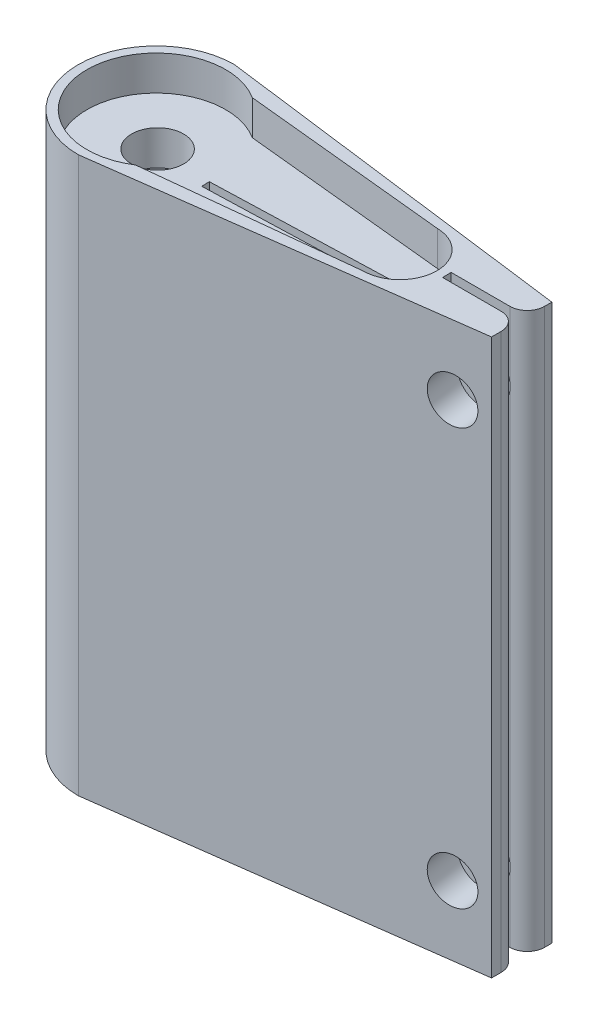
SolidWorks part; units mm, degrees
ref_plane "Front Plane" through (0, 0, 0) normal (0, 0, 1) x (1, 0, 0)
ref_plane "Top Plane" through (0, 0, 0) normal (0, 1, 0) x (1, 0, 0)
ref_plane "Right Plane" through (0, 0, 0) normal (1, 0, 0) x (0, 0, -1)
sketch "Sketch2" plane through (0, 0, 0) normal (0, 1, 0) x (1, 0, 0)
  line L0 (-24.822, 2.75) -> (-24.822, -2.75) construction
  line L1 (-26.9871, 0) -> (-9.8477, 0) construction
  line L2 (-5.9803, -0.2) -> (-5.98, -1.7573)
  line L3 (-5.9802, 0.3) -> (-10.372, 0.3)
  line L4 (-26.9871, 4.4282) -> (-5.9802, 1.719)
  line L5 (-26.9871, -4.5715) -> (-5.98, -1.7573)
  line L6 (-26.9871, 0) -> (-1.9871, 0) construction
  line L7 (-26.9871, -4.5715) -> (-2.3632, -1.0673) construction
  line L8 (-26.9871, 4.4282) -> (-5.9802, 2.3) construction
  line L9 (-10.372, 0.3) -> (-10.3556, -0.2)
  line L10 (-5.98, -1.7573) -> (-5.98, 5.1188) construction
  line L11 (-24.8218, 3.2918) -> (-12.9398, 2.0943)
  line L12 (-12.9872, -2.1664) -> (-24.8217, -3.4351)
  line L13 (-10.3556, -0.2) -> (-5.9803, -0.2)
  line L14 (-5.9802, 0.3) -> (-5.9802, 2.3)
  line L15 (-5.9802, 0.3) -> (-5.9802, -0.3836) construction
  circle A1 centre (-26.9871, 0) radius 1.5
  circle A3 centre (-26.9871, -0.0716) radius 4.4998
  circle A4 centre (-12.9872, -0.0358) radius 2.6366
  circle A6 centre (-12.9872, -0.0358) radius 2.1306
  circle A7 centre (-26.9871, -0.0716) radius 4.0002
  point P5 (-5.9802, -0.9787)
  dimension "D1" = 5.5
  dimension "D3" = 14
  dimension "D4" = 14
  dimension "D5" = 2
  dimension "D9" = 0
  dimension "D10" = 0
  dimension "D6" = 0
extrude "Boss-Extrude1" add sketch "Sketch2" along normal blind 30 contours A7 A1 | A7 L12 A3 L11 | A4 L11 A3 L12 | A6 L11 A4 L12 | A6 region at (-15.571, 0, 0.0394) region at (-19.2555, 0, 0.0535) region at (-24.3629, 0, 3.3143) region at (-12.9872, 0, 0.0358) region at (-30.8741, 0, 0.0717)
extrude "Boss-Extrude2" add sketch "Sketch2<3>" along normal blind 32 contours A7 L11 A3 L4 L5 L12 | A4 L12 A3 L5 | A4 L4 A3 L11 | A6 L12 A4 L9 L11 | A4 L3 L14 L4 | A4 L5 L2 L13 region at (-8.5849, 0, 1.2241) region at (-11.1062, 0, 1.788) region at (-19.5648, 0, 3.2424) region at (-8.6164, 0, -1.2462) region at (-26.4106, 0, 4.3754) region at (-19.5963, 0, -3.1385)
sketch "Sketch2<3>" plane through (0, 0, 0) normal (0, 1, 0) x (1, 0, 0) same geometry as "Sketch2"
fillet "Fillet3" radius 1 2 edges at (-5.9803, 16, 0.2) (-5.9802, 16, -0.3)
sketch "Sketch3" plane through (0.1258, 0, 0.9394) normal (0.1328, 0, 0.9911) x (0.9911, 0, -0.1328)
  line L0 (-27.3552, 16) -> (-6.0777, 16) construction
  line L1 (-27.3552, 32) -> (-27.3552, 0) construction
  line L2 (-6.0777, 0) -> (-6.0777, 32) construction
sketch "Sketch4" plane through (-10.3511, 0, 0.3386) normal (0.9995, 0, -0.0327) x (-0.0327, 0, -0.9995)
  line L0 (-3.6866, 16) -> (5.3082, 16) construction
  line L1 (-3.6866, 32) -> (-3.6866, 0) construction
  line L2 (5.3082, 32) -> (5.3082, 0) construction
  line L3 (0.634, 16) -> (0.639, 30)
  line L4 (0.639, 32) -> (0.639, 0) construction
  line L5 (0.639, 30) -> (0.1902, 30)
  line L6 (0.1902, 30) -> (0.1387, 16)
  line L7 (0.1387, 32) -> (0.1387, 0) construction
  line L8 (0.1387, 16) -> (0.634, 16)
  line L9 (0.1902, 2) -> (0.1387, 16)
  line L10 (0.639, 2) -> (0.1902, 2)
  line L11 (0.634, 16) -> (0.639, 2)
  dimension "D1" = 14
extrude "Cut-Extrude1" cut sketch "Sketch4" against normal blind 13.5 contours L11 L8 L9 L10 | L6 L8 L3 L5 region at (-10.3642, 22.885, -0.0614) region at (-10.3642, 9.115, -0.0614)
sketch "Sketch5" plane through (0.1258, 0, 0.9394) normal (0.1328, 0, 0.9911) x (0.9911, 0, -0.1328)
  line L0 (-8.1604, 32) -> (-8.1604, 0) construction
  line L1 (-27.3552, 32) -> (-6.1604, 32) construction
  line L2 (-27.3552, 0) -> (-6.1604, 0) construction
  line L3 (-6.1604, 32) -> (-6.1604, 0) construction
  line L4 (-27.3552, 16) -> (-6.0777, 16) construction
  circle A0 centre (-8.1604, 28) radius 1.3
  circle A1 centre (-8.1604, 4) radius 1.3
  dimension "D1" = 2
  dimension "D2" = 12
extrude "Cut-Extrude2" cut sketch "Sketch5" against normal through all
sketch "Sketch6" plane through (0, 0, 0) normal (0, -1, 0) x (1, 0, 0)
  circle A0 centre (-26.9871, 0) radius 3
extrude "Cut-Extrude3" cut sketch "Sketch6" against normal blind 28
